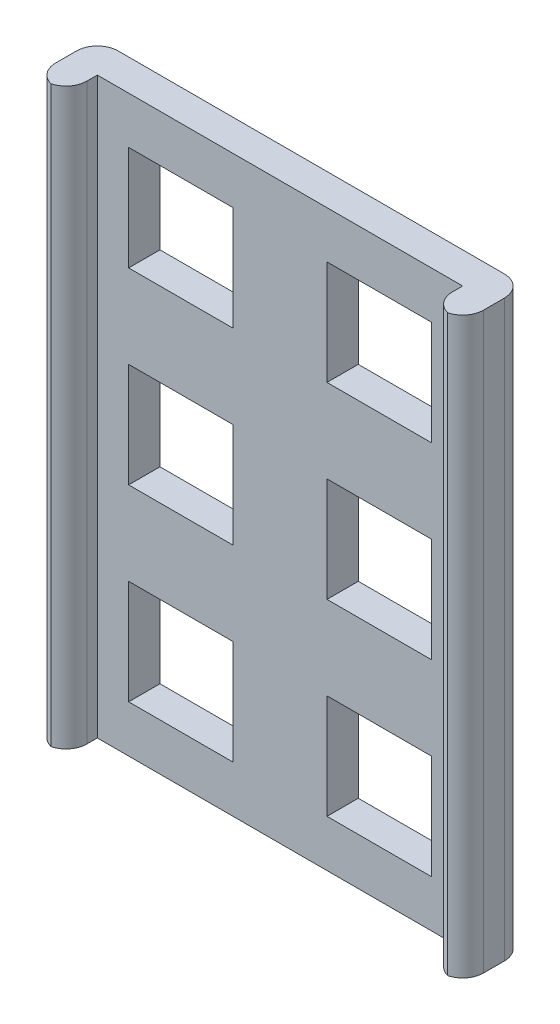
SolidWorks part; units mm, degrees
ref_plane "Alzado" through (0, 0, 0) normal (0, 0, 1) x (1, 0, 0)
ref_plane "Planta" through (0, 0, 0) normal (0, 1, 0) x (1, 0, 0)
ref_plane "Vista lateral" through (0, 0, 0) normal (1, 0, 0) x (0, 0, -1)
sketch "Croquis1" plane through (0, 0, 0) normal (0, 0, 1) x (1, 0, 0)
  line L1 (-92.9076, 35.1642) -> (-51.9076, 35.1642)
  line L2 (-92.9076, 35.1642) -> (-92.9076, -19.8358)
  line L3 (-92.9076, -19.8358) -> (-51.9076, -19.8358)
  line L4 (-51.9076, 35.1642) -> (-51.9076, -19.8358)
  dimension "D1" = 41
  dimension "D2" = 55
extrude "Saliente-Extruir1" add sketch "Croquis1" along normal blind 6
sketch "Croquis2" plane through (0, 0, 6) normal (0, 0, 1) x (1, 0, 0)
  line L0 (-51.9076, 35.1642) -> (-92.9076, 35.1642) construction
  line L1 (-89.9076, 35.1642) -> (-54.9076, 35.1642)
  line L2 (-89.9076, 35.1642) -> (-89.9076, -19.8358)
  line L3 (-89.9076, -19.8358) -> (-54.9076, -19.8358)
  line L4 (-54.9076, 35.1642) -> (-54.9076, -19.8358)
  line L5 (-92.9076, -19.8358) -> (-51.9076, -19.8358) construction
  line L6 (-92.9076, 35.1642) -> (-92.9076, -19.8358) construction
  line L7 (-51.9076, -19.8358) -> (-51.9076, 35.1642) construction
  dimension "D1" = 3
  dimension "D2" = 3
  dimension "D3" = 35
extrude "Cortar-Extruir1" cut sketch "Croquis2" against normal blind 3
fillet "Redondeo1" radius 2 6 edges at (-54.9076, 7.6642, 6) (-92.9076, 7.6642, 6) (-51.9076, 7.6642, 6) (-89.9076, 7.6642, 6) (-51.9076, 7.6642, 0) (-92.9076, 7.6642, 0)
sketch "Croquis3" plane through (0, 0, 0) normal (0, 0, -1) x (-1, 0, 0)
  line L1 (86.9076, -15.3358) -> (76.9076, -15.3358)
  line L2 (86.9076, -15.3358) -> (86.9076, -5.3358)
  line L3 (86.9076, -5.3358) -> (76.9076, -5.3358)
  line L4 (76.9076, -15.3358) -> (76.9076, -5.3358)
  line L5 (90.9076, -19.8358) -> (90.9076, 35.1642) construction
  line L6 (90.9076, -19.8358) -> (53.9076, -19.8358) construction
  line L8 (67.9076, -15.3358) -> (57.9076, -15.3358)
  line L9 (67.9076, -15.3358) -> (67.9076, -5.3358)
  line L10 (67.9076, -5.3358) -> (57.9076, -5.3358)
  line L11 (57.9076, -15.3358) -> (57.9076, -5.3358)
  line L12 (67.9076, 2.6642) -> (57.9076, 2.6642)
  line L13 (67.9076, 2.6642) -> (67.9076, 12.6642)
  line L14 (67.9076, 12.6642) -> (57.9076, 12.6642)
  line L15 (57.9076, 2.6642) -> (57.9076, 12.6642)
  line L16 (67.9076, 20.6642) -> (57.9076, 20.6642)
  line L17 (67.9076, 20.6642) -> (67.9076, 30.6642)
  line L18 (67.9076, 30.6642) -> (57.9076, 30.6642)
  line L19 (57.9076, 20.6642) -> (57.9076, 30.6642)
  line L20 (86.9076, 2.6642) -> (76.9076, 2.6642)
  line L21 (86.9076, 2.6642) -> (86.9076, 12.6642)
  line L22 (86.9076, 12.6642) -> (76.9076, 12.6642)
  line L23 (76.9076, 2.6642) -> (76.9076, 12.6642)
  line L24 (86.9076, 20.6642) -> (76.9076, 20.6642)
  line L25 (86.9076, 20.6642) -> (86.9076, 30.6642)
  line L26 (86.9076, 30.6642) -> (76.9076, 30.6642)
  line L27 (76.9076, 20.6642) -> (76.9076, 30.6642)
  dimension "D1" = 4
  dimension "D2" = 4.5
  dimension "D3" = 10
  dimension "D4" = 10
  dimension "D5" = 2
  dimension "D6" = 3
extrude "Cortar-Extruir2" cut sketch "Croquis3" against normal up to vertex (3 mm away) up to point (-54.9076, 35.1642, 3)
